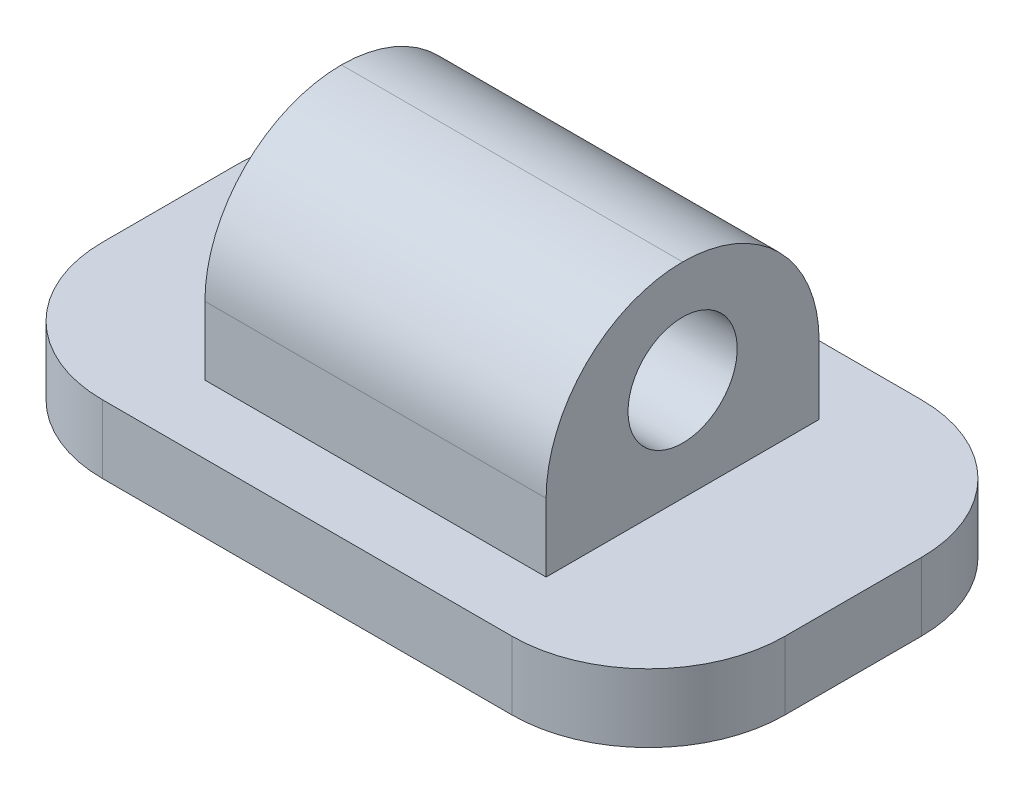
SolidWorks part; units mm, degrees
material "1.4000 (X6Cr13)"
ref_plane "Płaszczyzna przednia" through (0, 0, 0) normal (0, 0, 1) x (1, 0, 0)
ref_plane "Płaszczyzna górna" through (0, 0, 0) normal (0, 1, 0) x (1, 0, 0)
ref_plane "Płaszczyzna prawa" through (0, 0, 0) normal (1, 0, 0) x (0, 0, -1)
sketch "Szkic1" plane through (0, 0, 0) normal (0, 1, 0) x (1, 0, 0)
  line L1 (-25, -15) -> (25, -15)
  line L2 (-25, -15) -> (-25, 15)
  line L3 (-25, 15) -> (25, 15)
  line L4 (25, -15) -> (25, 15)
  line L5 (-25, -15) -> (25, 15) construction
  line L6 (-25, 15) -> (25, -15) construction
  point P0 (0, 0)
  dimension "D1" = 50
  dimension "D2" = 30
extrude "Dodanie-wyciągnięcie1" add sketch "Szkic1" along normal blind 5
fillet "Zaokrąglenie1" radius 10 4 edges at (25, 2.5, -15) (25, 2.5, 15) (-25, 2.5, 15) (-25, 2.5, -15)
sketch "Szkic2" plane through (0, 5, 0) normal (0, 1, 0) x (1, 0, 0)
  line L1 (-12.5, -10) -> (12.5, -10)
  line L2 (-12.5, -10) -> (-12.5, 10)
  line L3 (-12.5, 10) -> (12.5, 10)
  line L4 (12.5, -10) -> (12.5, 10)
  line L5 (-12.5, -10) -> (12.5, 10) construction
  line L6 (-12.5, 10) -> (12.5, -10) construction
  point P0 (0, 0)
  dimension "D1" = 20
  dimension "D2" = 25
extrude "Dodanie-wyciągnięcie2" add sketch "Szkic2" along normal blind 15
sketch "Szkic3" plane through (-12.5, 0, 0) normal (-1, 0, 0) x (0, 0, 1)
  line L0 (-10, 5) -> (10, 20) construction
  circle A0 centre (0, 12.5) radius 4
extrude "Wytnij-wyciągnięcie1" cut sketch "Szkic3" against normal blind 30
fillet "Zaokrąglenie2" radius 10 2 edges at (0, 20, 10) (0, 20, -10)
